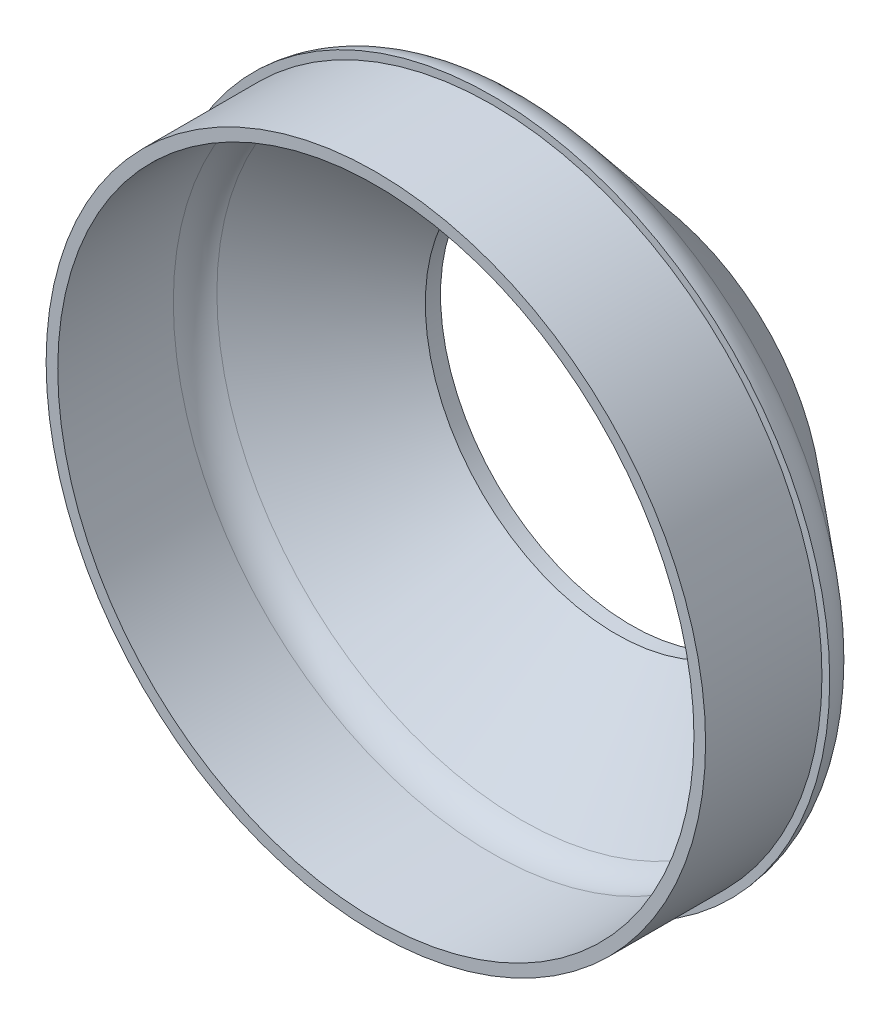
SolidWorks part; units mm, degrees
material "Thornel Mat VMA"
ref_plane "Front Plane" through (0, 0, 0) normal (0, 0, 1) x (1, 0, 0)
ref_plane "Top Plane" through (0, 0, 0) normal (0, 1, 0) x (1, 0, 0)
ref_plane "Right Plane" through (0, 0, 0) normal (1, 0, 0) x (0, 0, -1)
sketch "Sketch1" plane through (0, 0, 0) normal (1, 0, 0) x (0, 0, -1)
  line L0 (-24.0725, 81.9998) -> (10.3795, 81.9998)
  line L1 (10.3795, 81.9998) -> (37.8913, 49.2125)
  line L2 (37.8913, 49.2125) -> (41.8075, 49.2125)
  line L3 (41.8075, 49.2125) -> (10.1002, 86.9998)
  line L4 (10.1002, 86.9998) -> (5.9275, 86.9998)
  line L5 (5.9275, 86.9998) -> (5.9275, 84.9998)
  line L6 (5.9275, 84.9998) -> (-24.0725, 84.9998)
  line L7 (-24.0725, 84.9998) -> (-24.0725, 81.9998)
  point P2 (15.5933, 95.6622)
  point P9 (11.7558, 80.9757)
  dimension "D1" = 84.9998
  dimension "D2" = 35.88
  dimension "D3" = 49.2125
  dimension "D4" = 50
  dimension "D5" = 2
  dimension "D6" = 3
  dimension "D7" = 3
  dimension "D8" = 30
  dimension "D9" = 37.8913
ref_axis "Axis1" through (0, 0, 27.3665) along (0, 0, -1)
revolve "Revolve1" add sketch "Sketch1" angle 360 about axis through (0, 0, 27.3665) along (0, 0, -1)
fillet "Fillet1" radius 10 1 edges at (81.9998, 0, -10.3795)
fillet "Fillet2" radius 10 1 edges at (86.9998, 0, -10.1002)
